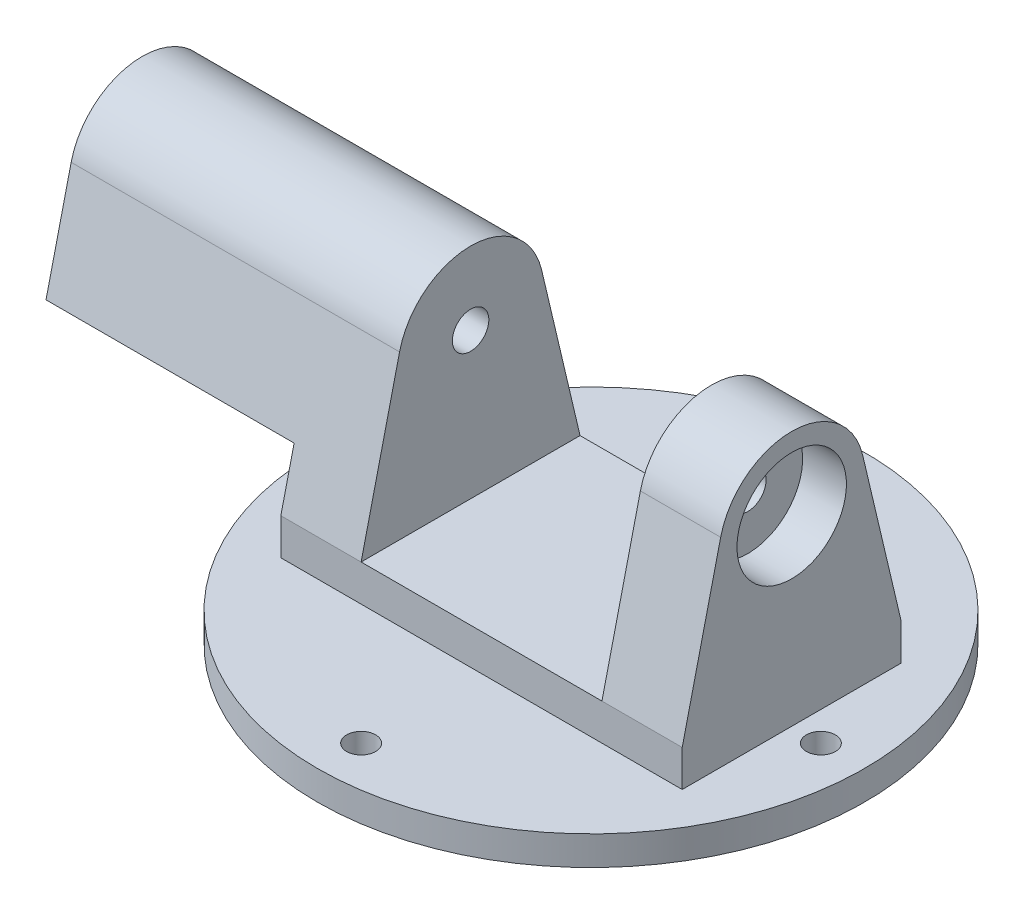
SolidWorks part; units mm, degrees
ref_plane "Alzado" through (0, 0, 0) normal (0, 0, 1) x (1, 0, 0)
ref_plane "Planta" through (0, 0, 0) normal (0, 1, 0) x (1, 0, 0)
ref_plane "Vista lateral" through (0, 0, 0) normal (1, 0, 0) x (0, 0, -1)
sketch "Croquis1" plane through (0, 0, 0) normal (0, 1, 0) x (1, 0, 0)
  circle A0 centre (0, 0) radius 75
extrude "Saliente-Extruir1" add sketch "Croquis1" along normal blind 8
sketch "Croquis2" plane through (0, 8, 0) normal (0, 1, 0) x (1, 0, 0)
  line L0 (0, 75) -> (0, 63) construction
  circle A0 centre (0, 0) radius 75 construction
  circle A1 centre (0, 63) radius 3.97
  circle A2 centre (63, 0) radius 3.97
  circle A3 centre (0, -63) radius 3.97
  circle A4 centre (-63, 0) radius 3.97
  point P15 (0, 0)
  dimension "D1" = 4
extrude "Cortar-Extruir1" cut sketch "Croquis2" against normal blind 20
sketch "Croquis3" plane through (0, 8, 0) normal (0, 1, 0) x (1, 0, 0)
  line L0 (-75, 0) -> (-55, 0) construction
  line L1 (75, 0) -> (55, 0) construction
  line L2 (-55, 0) -> (-55, 30)
  line L3 (-55, 30) -> (55, 30)
  line L4 (55, 30) -> (55, 0)
  line L5 (55, 0) -> (55, -30)
  line L6 (55, -30) -> (-55, -30)
  line L7 (-55, -30) -> (-55, 0)
  circle A0 centre (0, 0) radius 75 construction
extrude "Saliente-Extruir2" add sketch "Croquis3" along normal blind 10
sketch "Croquis4" plane through (55, 0, 0) normal (1, 0, 0) x (0, 0, -1)
  line L0 (-30, 18) -> (30, 18)
  line L2 (-30, 18) -> (-19.4643, 62.5982)
  line L3 (30, 18) -> (19.4643, 62.5982)
  arc A0 (19.4643, 62.5982) -> (-19.4643, 62.5982) centre (0, 58) ccw
extrude "Saliente-Extruir3" add sketch "Croquis4" against normal blind 22
mirror "Simetría1" about plane through (0, 0, 0) normal (1, 0, 0) of "Saliente-Extruir3"
sketch "Croquis5" plane through (-55, 0, 0) normal (-1, 0, 0) x (0, 0, 1)
  line L0 (0, 78) -> (0, 58) construction
  arc A0 (19.4643, 62.5982) -> (-19.4643, 62.5982) centre (0, 58) ccw construction
  circle A1 centre (0, 58) radius 15
extrude "Cortar-Extruir2" cut sketch "Croquis5" against normal blind 12
mirror "Simetría2" about plane through (0, 0, 0) normal (1, 0, 0) of "Cortar-Extruir2"
sketch "Croquis6" plane through (-43, 0, 0) normal (-1, 0, 0) x (0, 0, 1)
  line L0 (0, 73) -> (0, 58) construction
  circle A0 centre (0, 58) radius 15 construction
  circle A1 centre (0, 58) radius 5
extrude "Cortar-Extruir3" cut sketch "Croquis6" against normal blind 126
sketch "Croquis7" plane through (-55, 0, 0) normal (-1, 0, 0) x (0, 0, 1)
  line L0 (-19.4643, 62.5982) -> (-26.3615, 33.4018)
  line L1 (-30, 18) -> (-19.4643, 62.5982) construction
  line L2 (-26.3615, 33.4018) -> (26.3615, 33.4018)
  line L3 (19.4643, 62.5982) -> (30, 18) construction
  line L4 (26.3615, 33.4018) -> (19.4643, 62.5982)
  arc A0 (19.4643, 62.5982) -> (-19.4643, 62.5982) centre (0, 58) ccw
  circle A1 centre (0, 58) radius 15
extrude "Saliente-Extruir4" add sketch "Croquis7" along normal blind 68
